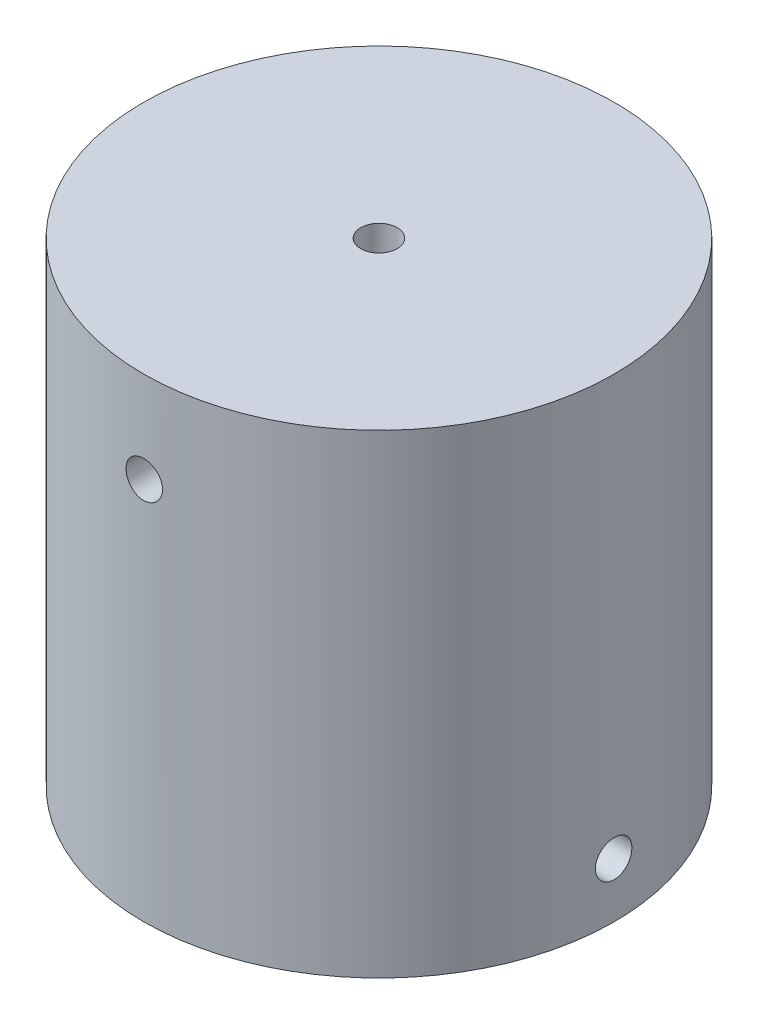
SolidWorks part; units mm, degrees
ref_plane "Front Plane" through (0, 0, 0) normal (0, 0, 1) x (1, 0, 0)
ref_plane "Top Plane" through (0, 0, 0) normal (0, 1, 0) x (1, 0, 0)
ref_plane "Right Plane" through (0, 0, 0) normal (1, 0, 0) x (0, 0, -1)
sketch "Sketch1" plane through (0, 0, 0) normal (0, 1, 0) x (1, 0, 0)
  line L6 (-2.0364, -1.6072) -> (-2.0364, -2.0545)
  line L7 (1.7636, -2.0545) -> (1.7636, -1.6072)
  line L8 (1.7636, -1.6072) -> (1.7636, 1.88)
  line L9 (1.7636, 1.88) -> (1.7636, 2.3273)
  line L10 (-2.0364, 2.3273) -> (-2.0364, 1.88)
  line L11 (-2.0364, 1.88) -> (-2.0364, -1.6072)
  arc A4 (-2.0364, -2.0545) -> (-0.1364, -2.7636) centre (-0.1364, 0.1364) ccw
  arc A5 (-0.1364, -2.7636) -> (1.7636, -2.0545) centre (-0.1364, 0.1364) ccw
  arc A6 (1.7636, 2.3273) -> (-0.1364, 3.0364) centre (-0.1364, 0.1364) ccw
  arc A7 (-0.1364, 3.0364) -> (-2.0364, 2.3273) centre (-0.1364, 0.1364) ccw
  circle A8 centre (-0.1364, 0.1364) radius 12.9
  dimension "D1" = 10
extrude "Boss-Extrude1" add sketch "Sketch1" along normal blind 6
sketch "Sketch2" plane through (0, 6, 0) normal (0, 1, 0) x (1, 0, 0)
  circle A1 centre (-0.1364, 0.1364) radius 12.9
  circle A2 centre (-0.1364, 0.1364) radius 12.9
  dimension "D1" = 0
extrude "Boss-Extrude2" add sketch "Sketch2" along normal blind 20
sketch "Sketch3" plane through (0, 26, 0) normal (0, 1, 0) x (1, 0, 0)
  circle A0 centre (-0.1364, 0.1364) radius 1
  dimension "D2" = 2
extrude "Cut-Extrude2" cut sketch "Sketch3" against normal blind 5
sketch "Sketch4" plane through (0, 0, 0) normal (1, 0, 0) x (0, 0, -1)
  line L0 (0.1364, 6) -> (0.1364, 0) construction
  line L4 (-2.0545, 0) -> (2.3273, 0)
  line L5 (2.3273, 0) -> (2.3273, 6)
  line L6 (2.3273, 6) -> (-2.0545, 6)
  line L7 (-2.0545, 6) -> (-2.0545, 0)
  line L8 (-2.0545, 0) -> (2.3273, 0)
  line L9 (2.3273, 0) -> (2.3273, 6)
  line L10 (2.3273, 6) -> (0.1364, 6)
  circle A0 centre (0.1364, 3) radius 1
  dimension "D2" = 2
  dimension "D1" = 0
extrude "Cut-Extrude3" cut sketch "Sketch4" against normal blind 19 and the other way blind 18 contours A0 L0 | L0 A0 region at (0, 3, -0.5608) region at (0, 3, 0.288)
sketch "Sketch5" plane through (0, 0, 0) normal (0, 0, 1) x (1, 0, 0)
  line L0 (0.8636, 26) -> (-1.1364, 26) construction
  line L1 (0.8636, 26) -> (-1.1364, 26)
  line L2 (0.8636, 21) -> (-1.1364, 21) construction
  line L3 (0.8636, 21) -> (-1.1364, 21)
  circle A0 centre (-0.1364, 21) radius 1
  dimension "D1" = 2
extrude "Cut-Extrude4" cut sketch "Sketch5" against normal blind 19 and the other way blind 19 contours L3 A0 | L3 A0 region at (-0.1364, 20.5756, 0) region at (-0.1364, 21.4244, 0)
sketch "Sketch6" plane through (0, 0, 0) normal (0, -1, 0) x (1, 0, 0)
  line L0 (-1.6364, -1.88) -> (-1.6364, -2.1364)
  line L1 (1.3636, -2.1364) -> (1.3636, -1.88)
  line L2 (-1.6364, 1.8636) -> (-1.6364, 1.6072)
  line L3 (1.3636, 1.6072) -> (1.3636, 1.8636)
  line L4 (1.3636, -1.88) -> (1.3636, 1.6072)
  line L5 (-1.6364, 1.6072) -> (-1.6364, -1.88)
  line L6 (-1.8364, -1.88) -> (-1.8364, -2.234)
  line L7 (1.5636, -2.234) -> (1.5636, -1.88)
  line L8 (1.5636, -1.88) -> (1.5636, 1.6072)
  line L9 (1.5636, 1.6072) -> (1.5636, 1.9612)
  line L10 (-1.8364, 1.9612) -> (-1.8364, 1.6072)
  line L11 (-1.8364, 1.6072) -> (-1.8364, -1.88)
  line L14 (1.7636, -2.3273) -> (1.7636, 2.0545)
  line L15 (-2.0364, 2.0545) -> (-2.0364, -2.3273)
  line L16 (1.7636, -2.3273) -> (1.7636, 2.0545)
  line L17 (-2.0364, 2.0545) -> (-2.0364, -2.3273)
  arc A0 (-1.6364, -2.1364) -> (-0.1364, -2.6364) centre (-0.1364, -0.1364) ccw
  arc A1 (-0.1364, -2.6364) -> (1.3636, -2.1364) centre (-0.1364, -0.1364) ccw
  arc A2 (-0.1364, 2.3636) -> (-1.6364, 1.8636) centre (-0.1364, -0.1364) ccw
  arc A3 (1.3636, 1.8636) -> (-0.1364, 2.3636) centre (-0.1364, -0.1364) ccw
  arc A6 (-1.8364, -2.234) -> (-0.1364, -2.8364) centre (-0.1364, -0.1364) ccw
  arc A7 (-0.1364, -2.8364) -> (1.5636, -2.234) centre (-0.1364, -0.1364) ccw
  arc A8 (1.5636, 1.9612) -> (-0.1364, 2.5636) centre (-0.1364, -0.1364) ccw
  arc A9 (-0.1364, 2.5636) -> (-1.8364, 1.9612) centre (-0.1364, -0.1364) ccw
  arc A12 (1.7636, 2.0545) -> (-2.0364, 2.0545) centre (-0.1364, -0.1364) ccw
  arc A13 (-2.0364, -2.3273) -> (1.7636, -2.3273) centre (-0.1364, -0.1364) ccw
  arc A14 (1.7636, 2.0545) -> (-2.0364, 2.0545) centre (-0.1364, -0.1364) ccw
  arc A15 (-2.0364, -2.3273) -> (1.7636, -2.3273) centre (-0.1364, -0.1364) ccw
  arc M6 (-2.0364, 2.0545) -> (1.7636, 2.0545) centre (-0.1364, -0.1364) cw
  line M7 (1.7636, 2.0545) -> (1.7636, -2.3273)
  arc M8 (1.7636, -2.3273) -> (-2.0364, -2.3273) centre (-0.1364, -0.1364) cw
  line M9 (-2.0364, -2.3273) -> (-2.0364, 2.0545)
  dimension "D1" = 0.2
  dimension "D2" = 0
extrude "Boss-Extrude3" add sketch "Sketch6" against normal up to surface (6 mm away) contours A9 A8 L9 L8 L7 A7 A6 L6 L11 L10 M6 M9 M8 M7 region at (-0.1364, 0, -2.9671) up to face at (-0.1364, 6, -0.1364)
sketch "Sketch7" plane through (0, 26, 0) normal (0, 1, 0) x (1, 0, 0)
  circle A0 centre (-0.1364, 0.1364) radius 1 construction
  arc A1 (0.8636, 0.1364) -> (-1.1364, 0.1364) centre (-0.1364, 0.1364) ccw construction
  circle A2 centre (-0.1364, 0.1364) radius 1
  arc A3 (0.8636, 0.1364) -> (-1.1364, 0.1364) centre (-0.1364, 0.1364) ccw
  circle M1 centre (-0.1364, 0.1364) radius 1
extrude "Cut-Extrude5" cut sketch "Sketch7" against normal blind 10 contours A2 M1 region at (-0.1364, 26, -0.1364)
